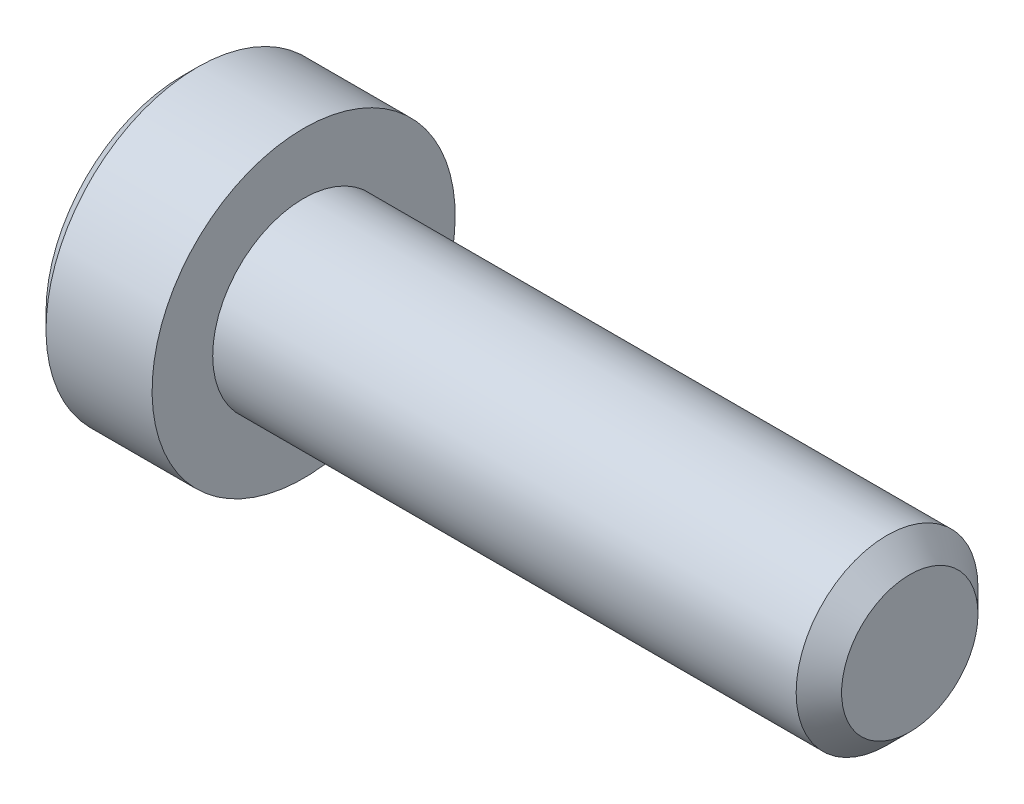
SolidWorks part; units mm, degrees
material "Alloy Steel"
ref_plane "Front Plane" through (0, 0, 0) normal (0, 0, 1) x (1, 0, 0)
ref_plane "Top Plane" through (0, 0, 0) normal (0, 1, 0) x (1, 0, 0)
ref_plane "Right Plane" through (0, 0, 0) normal (1, 0, 0) x (0, 0, -1)
sketch "Sketch1" plane through (0, 0, 0) normal (0, 0, 1) x (1, 0, 0)
  line L0 (10, 0) -> (-10, 0) construction
  line L1 (10, 3) -> (10, -3) construction
  line L2 (-10, 5) -> (-10, -5) construction
  line L3 (-10, 5) -> (-13.5, 5) construction
  line L4 (-13.5, 5) -> (-14, 4.5) construction
  line L5 (-14, 4.5) -> (-14, -4.5) construction
  line L6 (-14, -4.5) -> (-13.5, -5) construction
  line L7 (-13.5, -5) -> (-10, -5) construction
  point P7 (-10.88, 0)
  point P12 (6, -3)
  dimension "D1" = 45
  dimension "Dec." = 6
  dimension "Length" = 20
  dimension "Head Dia" = 10
  dimension "Head Height" = 4
  dimension "Hex Depth" = 3.12
  dimension "Chamfer" = 0.5
  dimension "D2" = 4
ref_plane "Plane1" through (10, 0, 0) normal (1, 0, 0) x (0, 0, -1)
ref_plane "Plane2" through (-14, 0, 0) normal (1, 0, 0) x (0, 0, -1)
sketch "Sketch2" plane through (10, 0, 0) normal (1, 0, 0) x (0, 0, -1)
  circle A0 centre (0, 0) radius 3
extrude "Boss-Extrude1" add sketch "Sketch2" against normal up to vertex (20 mm away) up to point (-10, 0, 0)
sketch "Sketch3" plane through (10, 0, 0) normal (1, 0, 0) x (0, 0, -1)
  circle A0 centre (0, 0) radius 3 construction
  circle A1 centre (0, 0) radius 3
curve "Helix/Spiral1" pitch 1 height 21 turns 21 parameters "Pitch"=1
chamfer "Chamfer1" distance 0.75 angle 45 1 edges at (10, 0, -3)
sketch "Sketch5" plane through (0, 0, 0) normal (0, 0, 1) x (1, 0, 0)
  line L0 (9.5625, 3) -> (10.4375, 3)
  line L1 (10.4375, 3) -> (10.0625, 2.3505)
  line L2 (10.0625, 2.3505) -> (9.9375, 2.3505)
  line L3 (9.9375, 2.3505) -> (9.5625, 3)
  line L4 (10, 2.3505) -> (10, 3) construction
  line L5 (9.75, 2.6752) -> (10.25, 2.6752) construction
  dimension "D1" = 60
  dimension "D2" = 0.5
  dimension "D3" = 0.125
sweep "Cut-Sweep1" [suppressed] cut profiles "Sketch5" path "Helix/Spiral1"
sketch "Sketch4" plane through (-14, 0, 0) normal (1, 0, 0) x (0, 0, -1)
  line L0 (-5, 0.7937) -> (5, 0.7937) construction
  line L1 (0, 2.3094) -> (-2, 1.1547)
  line L2 (-2, 1.1547) -> (-2, -1.1547)
  line L3 (-2, -1.1547) -> (0, -2.3094)
  line L4 (0, -2.3094) -> (2, -1.1547)
  line L5 (2, -1.1547) -> (2, 1.1547)
  line L6 (2, 1.1547) -> (0, 2.3094)
  line L7 (0, 0) -> (0, 0.7937) construction
  circle A0 centre (0, 0) radius 2 construction
  dimension "Hex Size" = 4
  dimension "D1" = 10
  dimension "D2" = 0.7937
sketch "Sketch6" plane through (0, 0, 0) normal (0, 0, 1) x (1, 0, 0)
  line L0 (-13.5, 5) -> (-14, 4.5) construction
  line L1 (-10, 5) -> (-13.5, 5) construction
  line L2 (-10, 5) -> (-10, -5) construction
  line L3 (-14, 4.5) -> (-14, -4.5) construction
  line L4 (-13.5, 5) -> (-14, 4.5)
  line L5 (-10, 5) -> (-13.5, 5)
  line L6 (-10, 5) -> (-10, 0)
  line L7 (-14, 4.5) -> (-14, 0)
  line L8 (-10, 0) -> (-14, 0) construction
  line L9 (-10, 0) -> (-14, 0)
revolve "Revolve1" add sketch "Sketch6" angle 360 about L8
extrude "Cut-Extrude1" cut sketch "Sketch4" along normal up to vertex (3.12 mm away) up to point (-10.88, 0, 0)
sketch "Sketch8" plane through (-14, 0, 0) normal (-1, 0, 0) x (0, 0, 1)
  circle A1 centre (0, 0) radius 2.3094
extrude "Cut-Extrude2" cut sketch "Sketch8" against normal through all draft 45
equation "\"D3@Helix/Spiral1\" = \"Length@Sketch1\"+\"Pitch@Helix/Spiral1\""
equation "\"D3@Sketch5\" = \"Pitch@Helix/Spiral1\"*.125"
equation "\"D2@Sketch5\" = \"Pitch@Helix/Spiral1\"*.50"
equation "\"D1@Chamfer1\" = \"Pitch@Helix/Spiral1\"*.75"
equation "\"D2@Sketch1\" = \"Pitch@Helix/Spiral1\"*4"
equation "\"D1@Sketch4\" = \"Head Dia@Sketch1\""
equation "\"Chamfer@Sketch1\" = \"Head Height@Sketch1\"/8"
